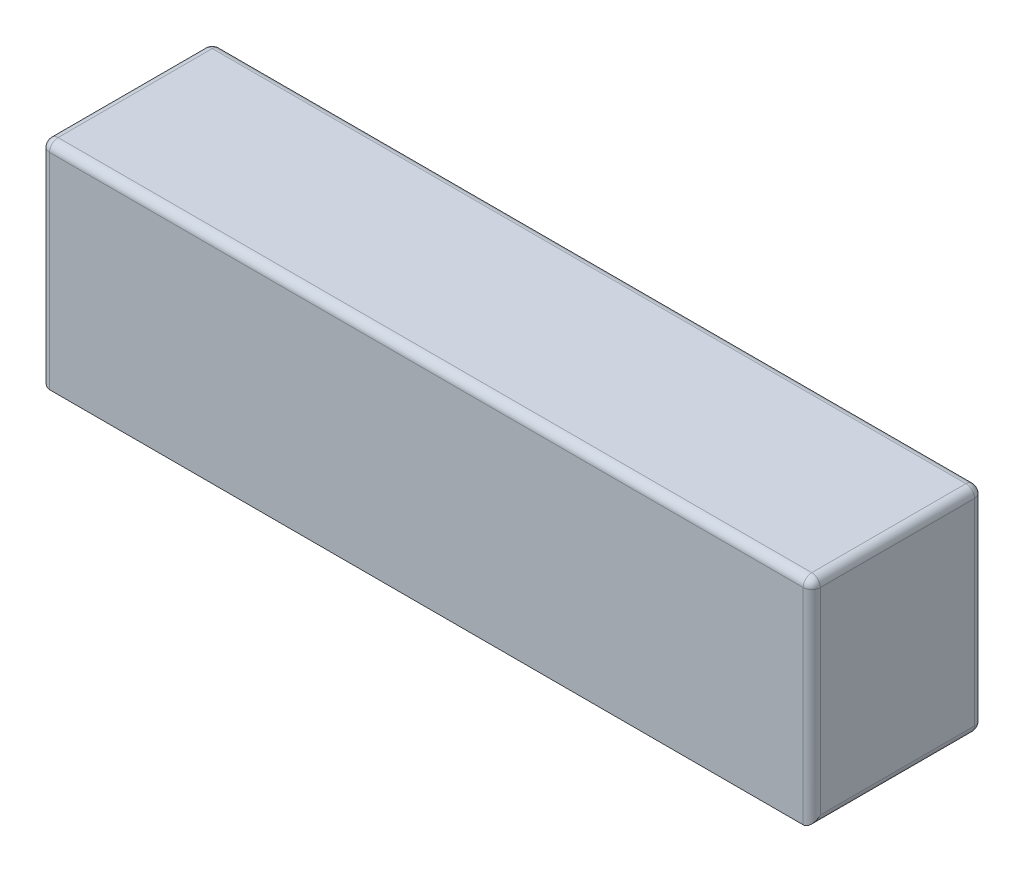
SolidWorks part; units mm, degrees
ref_plane "前基準面" through (0, 0, 0) normal (0, 0, 1) x (1, 0, 0)
ref_plane "上基準面" through (0, 0, 0) normal (0, 1, 0) x (1, 0, 0)
ref_plane "右基準面" through (0, 0, 0) normal (1, 0, 0) x (0, 0, -1)
sketch "草圖1" plane through (0, 0, 0) normal (0, 0, 1) x (1, 0, 0)
  line L0 (-81.2682, -47.6337) -> (8.7318, -47.6337)
  line L1 (8.7318, -47.6337) -> (8.7318, -22.6337)
  line L2 (8.7318, -22.6337) -> (-81.2682, -22.6337)
  line L3 (-81.2682, -22.6337) -> (-81.2682, -47.6337)
extrude "填料-伸長1" add sketch "草圖1" along normal blind 20 contours L2 L3 L0 L1
sketch "草圖4" plane through (0, 0, 0) normal (0, 0, -1) x (-1, 0, 0)
  line L0 (36.2682, -22.6337) -> (36.2682, -47.6337) construction
  line L1 (-8.7318, -22.6337) -> (81.2682, -22.6337) construction
  line L2 (81.2682, -47.6337) -> (-8.7318, -47.6337) construction
  line L3 (-8.7318, -47.6337) -> (-8.7318, -22.6337) construction
  line L4 (-6.7318, -24.6337) -> (35.5146, -24.6337)
  line L5 (-6.7318, -24.6337) -> (-6.7318, -45.6337)
  line L6 (-6.7318, -45.6337) -> (35.5146, -45.6337)
  line L7 (35.5146, -24.6337) -> (35.5146, -45.6337)
  line L8 (79.2682, -45.6337) -> (37.0218, -45.6337)
  line L9 (37.0218, -24.6337) -> (37.0218, -45.6337)
  line L10 (79.2682, -24.6337) -> (37.0218, -24.6337)
  line L11 (79.2682, -24.6337) -> (79.2682, -45.6337)
  dimension "D1" = 2
  dimension "D2" = 2
  dimension "D3" = 0.7536
  dimension "D4" = 2
extrude "除料-伸長2" cut sketch "草圖4" against normal blind 18
fillet "圓角5" radius 1 30 edges at (-79.2682, -35.1337, 0) (-14.3914, -45.6337, 0) (-36.2682, -47.6337, 0) (-79.2682, -45.6337, 9) (-37.0218, -45.6337, 9) (-58.145, -45.6337, 0) (-58.145, -45.6337, 18) (-37.0218, -35.1337, 0) (-79.2682, -35.1337, 18) (-58.145, -24.6337, 0) (-14.3914, -24.6337, 0) (-58.145, -24.6337, 18) (6.7318, -35.1337, 0) (-35.5146, -35.1337, 0) (-14.3914, -45.6337, 18) (-14.3914, -24.6337, 18) (6.7318, -24.6337, 9) (-35.5146, -24.6337, 9) (6.7318, -45.6337, 9) (8.7318, -47.6337, 10) (8.7318, -35.1337, 0) (8.7318, -35.1337, 20) (-35.5146, -45.6337, 9) (-81.2682, -47.6337, 10) (-81.2682, -35.1337, 0) (-81.2682, -35.1337, 20) (-81.2682, -22.6337, 10) (8.7318, -22.6337, 10) (-36.2682, -22.6337, 20) (-36.2682, -22.6337, 0)
